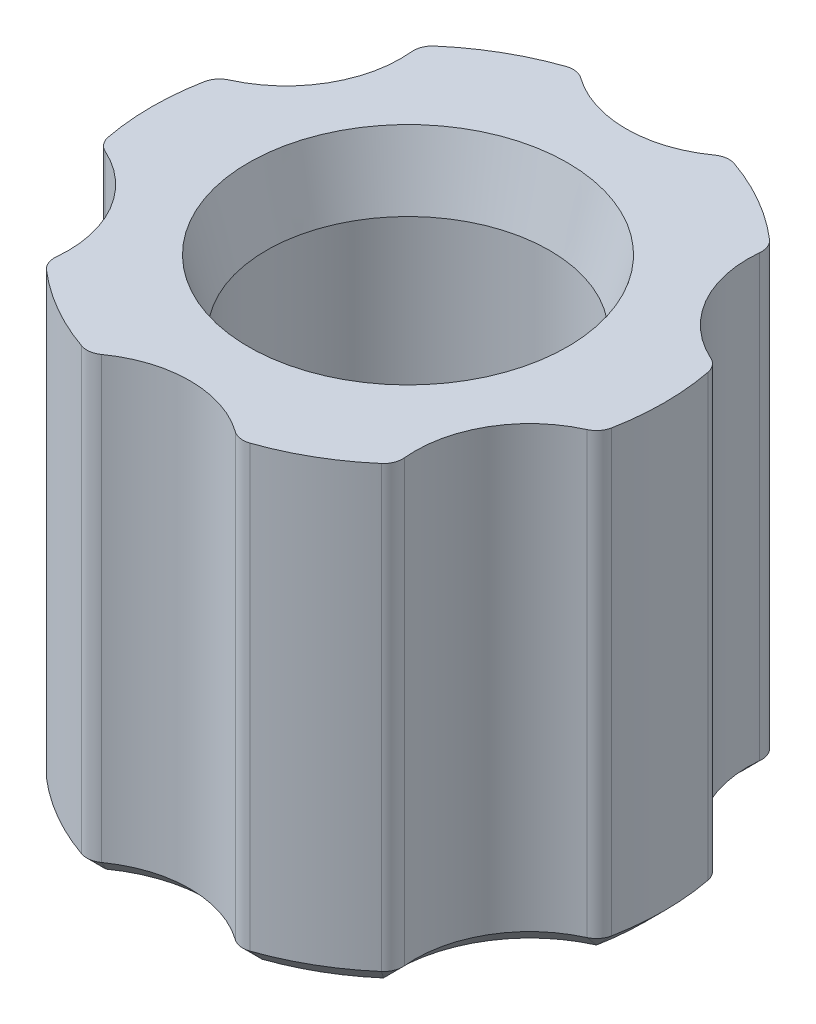
SolidWorks part; units mm, degrees
ref_plane "Front Plane" through (0, 0, 0) normal (0, 0, 1) x (1, 0, 0)
ref_plane "Top Plane" through (0, 0, 0) normal (0, 1, 0) x (1, 0, 0)
ref_plane "Right Plane" through (0, 0, 0) normal (1, 0, 0) x (0, 0, -1)
sketch "Sketch1" plane through (0, 0, 0) normal (1, 0, 0) x (0, 0, -1)
  line L0 (0, 0) -> (0, 27.5367) construction
  line L1 (0, 0) -> (-6.7, 0)
  line L2 (-6.7, 0) -> (-6.7, 12)
  line L3 (-6.7, 12) -> (-3.7, 12)
  line L5 (-3.7, 12) -> (-3.7, 4.2685)
  line L6 (-3.7, 4.2685) -> (-4.1, 2)
  line L7 (-4.1, 2) -> (0, 2)
  line L8 (0, 2) -> (0, 0)
  point P4 (-3.625, 3.9578)
  point P7 (-4, 3.142)
  point P11 (-3.625, 18.2854)
  point P12 (0, 0)
  point P13 (-3.625, 19.2621)
  dimension "D1" = 80
  dimension "D2" = 7.4
  dimension "D3" = 8.2
  dimension "D4" = 3
  dimension "D5" = 12
  dimension "D6" = 13.4
  dimension "D7" = 2
revolve "Revolve1" add sketch "Sketch1" angle 360 about L0
chamfer "Chamfer1" distance 1.75 angle 15 1 edges at (0, 12, -3.7) first distance on face at (0, 12, -3.7)
sketch "Sketch2" plane through (0, 0, 0) normal (0, 1, 0) x (1, 0, 0)
  circle A0 centre (0, 8.7) radius 3
  circle A2 centre (0, 0) radius 6.7 construction
  point P4 (0, 0)
  dimension "D1" = 1
  dimension "D2" = 6
extrude "Cut-Extrude1" cut sketch "Sketch2" along normal through all
pattern_circular "CirPattern1" count 6 over 360 of "Cut-Extrude1"
fillet "Fillet1" radius 0.5 12 edges at (6.5241, 6, -1.5253) (4.5829, 6, -4.8874) (4.5829, 6, 4.8874) (6.5241, 6, 1.5253) (-1.9411, 6, 6.4126) (1.9411, 6, 6.4126) (-6.5241, 6, 1.5253) (-4.5829, 6, 4.8874) (-4.5829, 6, -4.8874) (-6.5241, 6, -1.5253) (-1.9411, 6, -6.4126) (1.9411, 6, -6.4126)
chamfer "Chamfer2" distance 0.5 angle 45 24 edges at (4.9363, 0, -2.85) (6.483, 0, -1.4712) (4.5156, 0, -4.8789) (6.7, 0, 0) (3.35, 0, -5.8024) (6.483, 0, 1.4712) (1.9674, 0, -6.35) (4.9363, 0, 2.85) (0, 0, -5.7) (4.5156, 0, 4.8789) (-1.9674, 0, -6.35) (3.35, 0, 5.8024) (-3.35, 0, -5.8024) (1.9674, 0, 6.35) (-4.5156, 0, -4.8789) (0, 0, 5.7) (-4.9363, 0, -2.85) (-1.9674, 0, 6.35) (-6.483, 0, -1.4712) (-3.35, 0, 5.8024) (-6.7, 0, 0) (-4.5156, 0, 4.8789) (-6.483, 0, 1.4712) (-4.9363, 0, 2.85)
